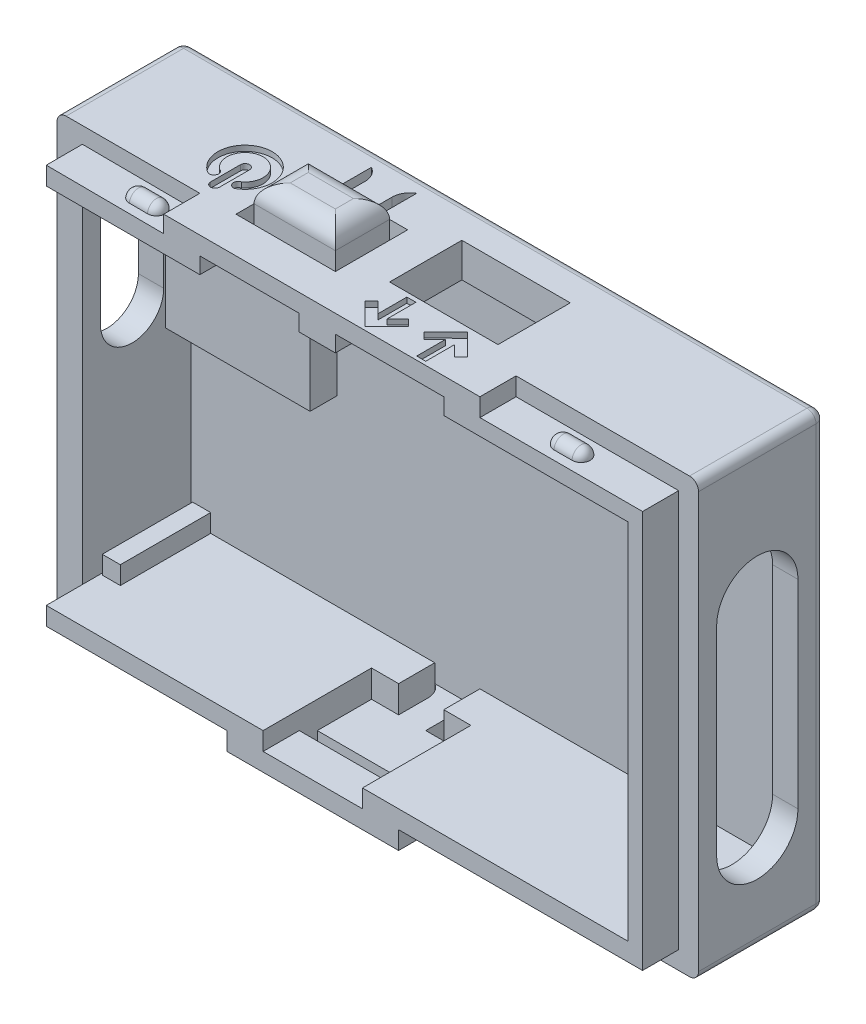
SolidWorks part; units mm, degrees
ref_plane "前视基准面" through (0, 0, 0) normal (0, 0, 1) x (1, 0, 0)
ref_plane "上视基准面" through (0, 0, 0) normal (0, 1, 0) x (1, 0, 0)
ref_plane "右视基准面" through (0, 0, 0) normal (1, 0, 0) x (0, 0, -1)
sketch "草图1" plane through (0, 0, 0) normal (0, 0, 1) x (1, 0, 0)
  line L5 (-17.75, 12) -> (17.75, 12)
  line L6 (-17.75, 12) -> (-17.75, -12)
  line L7 (-17.75, -12) -> (17.75, -12)
  line L8 (17.75, 12) -> (17.75, -12)
  line L9 (-17.75, 12) -> (17.75, -12) construction
  line L10 (-17.75, -12) -> (17.75, 12) construction
  point P0 (0, 0)
  dimension "D1" = 35.5
  dimension "D2" = 24
extrude "凸台-拉伸1" add sketch "草图1" along normal blind 7
sketch "草图2" plane through (0, 0, 7) normal (0, 0, 1) x (1, 0, 0)
  line L5 (-16.35, 11.1) -> (16.85, -11) construction
  line L6 (-16.35, -11) -> (16.85, 11.1) construction
  line L9 (-17.75, 12) -> (-17.75, -12) construction
  line L10 (-16.35, 11.1) -> (16.85, 11.1)
  line L11 (-16.35, 11.1) -> (-16.35, -11)
  line L12 (-16.35, -11) -> (16.85, -11)
  line L13 (16.85, 11.1) -> (16.85, -11)
  line L15 (17.75, 12) -> (-17.75, 12) construction
  line L16 (17.75, -12) -> (17.75, 12) construction
  point P0 (0, 0)
  dimension "D1" = 1.4
  dimension "D2" = 0.9
  dimension "D3" = 0.9
  dimension "D4" = 22.1
extrude "切除-拉伸1" cut sketch "草图2" against normal blind 6
sketch "草图3" plane through (-17.75, 0, 0) normal (-1, 0, 0) x (0, 0, 1)
  line L0 (4.25, 7.45) -> (4.25, 1.95) construction
  line L1 (6, 7.45) -> (6, 1.95)
  line L2 (2.5, 7.45) -> (2.5, 1.95)
  line L3 (0, 12) -> (0, -12) construction
  line L4 (7, 12) -> (0, 12) construction
  arc A0 (6, 7.45) -> (2.5, 7.45) centre (4.25, 7.45) ccw
  arc A1 (2.5, 1.95) -> (6, 1.95) centre (4.25, 1.95) ccw
  point P2 (4.25, 4.7)
  dimension "D3" = 5.5
  dimension "D4" = 4.55
  dimension "D1" = 2.5
  dimension "D2" = 3.5
extrude "切除-拉伸2" cut sketch "草图3" against normal blind 2
sketch "草图6" plane through (0, 0, 1) normal (0, 0, 1) x (1, 0, 0)
  line L14 (-16.35, 10.1) -> (15.85, 10.1)
  line L15 (-16.35, 11.1) -> (-16.35, -11) construction
  line L16 (15.85, 10.1) -> (15.85, -10)
  line L17 (15.85, -10) -> (-16.35, -10)
  line L18 (-16.35, -10) -> (-16.35, -11)
  line L19 (-16.35, -11) -> (16.85, -11)
  line L20 (16.85, -11) -> (16.85, 11.1)
  line L21 (16.85, 11.1) -> (-16.35, 11.1)
  line L22 (-16.35, 11.1) -> (-16.35, 10.1)
  dimension "D1" = 1
  dimension "D2" = 1
  dimension "D3" = 1
extrude "凸台-拉伸2" add sketch "草图6" along normal blind 6
sketch "草图7" plane through (0, 0, 1) normal (0, 0, 1) x (1, 0, 0)
  line L23 (15.85, 10.1) -> (10.85, 10.1)
  line L24 (15.85, 10.1) -> (15.85, 8.1)
  line L25 (15.85, 8.1) -> (10.85, 8.1)
  line L26 (10.85, 10.1) -> (10.85, 8.1)
  dimension "D3" = 5
  dimension "D8" = 2
extrude "凸台-拉伸3" add sketch "草图7" along normal blind 5
sketch "草图10" plane through (15.85, 0, 0) normal (-1, 0, 0) x (0, 0, 1)
  line L0 (3.75, -6.45) -> (3.75, 4.55) construction
  line L1 (1.5, -6.45) -> (1.5, 4.55)
  line L2 (6, -6.45) -> (6, 4.55)
  line L4 (7, -12) -> (0, -12) construction
  line L5 (7, -12) -> (7, 12) construction
  arc A0 (1.5, -6.45) -> (6, -6.45) centre (3.75, -6.45) ccw
  arc A1 (6, 4.55) -> (1.5, 4.55) centre (3.75, 4.55) ccw
  point P2 (3.75, -0.95)
  point P7 (3.75, 6.8)
  point P8 (3.75, -8.7)
  dimension "D2" = 15.5
  dimension "D1" = 4.5
  dimension "D3" = 1
  dimension "D4" = 3.3
extrude "切除-拉伸4" cut sketch "草图10" against normal blind 2
sketch "草图12" plane through (0, 0, 7) normal (0, 0, 1) x (1, 0, 0)
  line L0 (-16.35, 10.1) -> (-16.35, -10) construction
  line L8 (15.85, -10) -> (-16.35, -10) construction
  line L9 (-4.35, -10) -> (1.15, -10)
  line L10 (-4.35, -10) -> (-4.35, -12)
  line L11 (-4.35, -12) -> (1.15, -12)
  line L12 (1.15, -10) -> (1.15, -12)
  line L15 (-16.35, 10.1) -> (-16.35, -10) construction
  dimension "D1" = 12
  dimension "D2" = 17.5
  dimension "D3" = 2
extrude "切除-拉伸6" cut sketch "草图12" against normal blind 6
sketch "草图19" plane through (0, 0, 1) normal (0, 0, 1) x (1, 0, 0)
  line L0 (-16.35, 10.1) -> (10.85, 10.1) construction
  line L1 (-16.25, 10.1) -> (-8.25, 10.1)
  line L2 (-16.25, 10.1) -> (-16.25, 0.1)
  line L3 (-16.25, 0.1) -> (-8.25, 0.1)
  line L4 (-8.25, 10.1) -> (-8.25, 0.1)
  dimension "D1" = 8
  dimension "D2" = 0
  dimension "D3" = 10
extrude "USB支撑" add sketch "草图19" along normal blind 1.5
sketch "草图25" plane through (0, 0, 7) normal (0, 0, 1) x (1, 0, 0)
  line L0 (1.15, -12) -> (17.75, -12) construction
  line L2 (15.85, 8.1) -> (16.35, 8.1)
  line L3 (15.85, 8.1) -> (15.85, -10)
  line L4 (15.85, -10) -> (16.35, -10)
  line L5 (16.35, 8.1) -> (16.35, -10)
  line L7 (-16.35, 10.1) -> (15.85, 10.1) construction
  line L8 (15.85, 10.1) -> (15.85, -10) construction
  dimension "D1" = 2
  dimension "D2" = 2
  dimension "D3" = 0
  dimension "D4" = 0.5
extrude "切除-拉伸12" cut sketch "草图25" against normal blind 6
sketch "草图28" plane through (0, 0, 7) normal (0, 0, 1) x (1, 0, 0)
  line L0 (-16.35, 10.1) -> (15.85, 10.1) construction
  line L1 (-7.85, 10.1) -> (-2.35, 10.1)
  line L2 (-7.85, 10.1) -> (-7.85, 12)
  line L3 (-7.85, 12) -> (-2.35, 12)
  line L4 (-2.35, 10.1) -> (-2.35, 12)
  line L5 (17.75, 12) -> (-17.75, 12) construction
  line L6 (-16.35, 1.95) -> (-16.35, 7.45) construction
  dimension "D1" = 8.5
  dimension "D2" = 5.5
extrude "切除-拉伸13" cut sketch "草图28" against normal blind 6
sketch "草图29" plane through (0, 0, 7) normal (0, 0, 1) x (1, 0, 0)
  line L1 (-0.35, 10) -> (5.65, 10)
  line L2 (-0.35, 10) -> (-0.35, 12)
  line L3 (-0.35, 12) -> (5.65, 12)
  line L4 (5.65, 10) -> (5.65, 12)
  line L5 (17.75, 12) -> (-2.35, 12) construction
  line L8 (-16.35, 10.1) -> (-16.35, -10) construction
  dimension "D1" = 16
  dimension "D2" = 6
extrude "切除-拉伸14" cut sketch "草图29" against normal blind 5
sketch "草图34" plane through (0, 0, 1) normal (0, 0, 1) x (1, 0, 0)
  line L0 (16.35, -10) -> (1.15, -10) construction
  line L1 (-16.25, -9) -> (-15.25, -9)
  line L2 (-16.25, -9) -> (-16.25, -10)
  line L3 (-16.25, -10) -> (-15.25, -10)
  line L4 (-15.25, -9) -> (-15.25, -10)
  dimension "D1" = 1
  dimension "D2" = 1
extrude "凸台-拉伸10" add sketch "草图34" along normal blind 5
sketch "草图37" plane through (0, 0, 1) normal (0, 0, 1) x (1, 0, 0)
  line L0 (-4.35, -12) -> (1.15, -12) construction
  line L1 (-3.85, -12) -> (0.65, -12)
  line L2 (-3.85, -12) -> (-3.85, -10)
  line L3 (-3.85, -10) -> (0.65, -10)
  line L4 (0.65, -12) -> (0.65, -10)
  line L5 (1.15, -12) -> (1.15, -10) construction
  line L6 (-4.35, -10) -> (-4.35, -12) construction
  dimension "D1" = 0.5
  dimension "D2" = 0.5
  dimension "D3" = 2
extrude "凸台-拉伸12" add sketch "草图37" along normal blind 5.5
sketch "草图38" plane through (0, -12, 0) normal (0, -1, 0) x (1, 0, 0)
  line L1 (-3.85, 1) -> (-2.35, 1)
  line L2 (-3.85, 1) -> (-3.85, 3.5)
  line L3 (-3.85, 3.5) -> (-2.35, 3.5)
  line L4 (-2.35, 1) -> (-2.35, 3.5)
  line L5 (0.65, 1) -> (-0.85, 1)
  line L6 (0.65, 1) -> (0.65, 3.5)
  line L7 (0.65, 3.5) -> (-0.85, 3.5)
  line L8 (-0.85, 1) -> (-0.85, 3.5)
  dimension "D1" = 2.5
  dimension "D2" = 2.5
  dimension "D3" = 1.5
  dimension "D4" = 1.5
extrude "切除-拉伸16" cut sketch "草图38" against normal blind 2
sketch "草图39" plane through (0, 0, 6.5) normal (0, 0, 1) x (1, 0, 0)
  line L0 (0.65, -12) -> (0.65, -10) construction
  line L1 (-3.85, -10) -> (0.65, -10)
  line L2 (-3.85, -10) -> (-3.85, -11)
  line L3 (-3.85, -11) -> (0.65, -11)
  line L4 (0.65, -10) -> (0.65, -11)
  dimension "D1" = 1
extrude "切除-拉伸17" cut sketch "草图39" against normal blind 5.5
sketch "草图40" plane through (0, -12, 0) normal (0, -1, 0) x (1, 0, 0)
  line L0 (0.65, 6.5) -> (0.65, 3.5) construction
  line L1 (-3.85, 6.5) -> (0.65, 6.5)
  line L2 (-3.85, 6.5) -> (-3.85, 3.5)
  line L3 (-3.85, 3.5) -> (0.65, 3.5)
  line L4 (0.65, 6.5) -> (0.65, 3.5)
  line L6 (-3.85, 6.5) -> (0.65, 6.5) construction
  dimension "D1" = 3
  dimension "D2" = 0
  dimension "D3" = 4.5
extrude "凸台-拉伸13" add sketch "草图40" along normal blind 1.5
fillet "圆角2" radius 1 4 edges at (-1.6, -13.5, 3.5) (0.65, -13.5, 5) (-1.6, -13.5, 6.5) (-3.85, -13.5, 5)
sketch "草图41" plane through (0, 0, 1) normal (0, 0, 1) x (1, 0, 0)
  line L0 (-2.35, 12) -> (-7.85, 12) construction
  line L1 (-7.35, 12) -> (-2.85, 12)
  line L2 (-7.35, 12) -> (-7.35, 10)
  line L3 (-7.35, 10) -> (-2.85, 10)
  line L4 (-2.85, 12) -> (-2.85, 10)
  line L5 (-2.35, 10.1) -> (-2.35, 12) construction
  line L6 (-7.85, 12) -> (-7.85, 10.1) construction
  dimension "D1" = 0.5
  dimension "D2" = 0.5
  dimension "D3" = 2
extrude "凸台-拉伸14" add sketch "草图41" along normal blind 5.5
sketch "草图42" plane through (0, 12, 0) normal (0, 1, 0) x (1, 0, 0)
  line L1 (-7.35, -1) -> (-5.85, -1)
  line L2 (-7.35, -1) -> (-7.35, -3.5)
  line L3 (-7.35, -3.5) -> (-5.85, -3.5)
  line L4 (-5.85, -1) -> (-5.85, -3.5)
  line L5 (-2.85, -1) -> (-4.35, -1)
  line L6 (-2.85, -1) -> (-2.85, -3.5)
  line L7 (-2.85, -3.5) -> (-4.35, -3.5)
  line L8 (-4.35, -1) -> (-4.35, -3.5)
  dimension "D1" = 1.5
  dimension "D2" = 1.5
  dimension "D3" = 2.5
  dimension "D4" = 2.5
extrude "切除-拉伸18" cut sketch "草图42" against normal blind 2
sketch "草图43" plane through (0, 0, 6.5) normal (0, 0, 1) x (1, 0, 0)
  line L0 (-2.85, 10) -> (-2.85, 12) construction
  line L1 (-7.35, 10) -> (-2.85, 10)
  line L2 (-7.35, 10) -> (-7.35, 11)
  line L3 (-7.35, 11) -> (-2.85, 11)
  line L4 (-2.85, 10) -> (-2.85, 11)
extrude "切除-拉伸19" cut sketch "草图43" against normal blind 5.5
sketch "草图44" plane through (0, 12, 0) normal (0, 1, 0) x (1, 0, 0)
  line L0 (-2.85, -6.5) -> (-2.85, -3.5) construction
  line L1 (-7.35, -6.5) -> (-2.85, -6.5)
  line L2 (-7.35, -6.5) -> (-7.35, -3.5)
  line L3 (-7.35, -3.5) -> (-2.85, -3.5)
  line L4 (-2.85, -6.5) -> (-2.85, -3.5)
  dimension "D1" = 3
extrude "凸台-拉伸15" add sketch "草图44" along normal blind 1.5
fillet "圆角3" radius 1 4 edges at (-2.85, 13.5, 5) (-5.1, 13.5, 3.5) (-7.35, 13.5, 5) (-5.1, 13.5, 6.5)
sketch "草图45" plane through (0, 0, 7) normal (0, 0, 1) x (1, 0, 0)
  line L0 (-7.85, 10.1) -> (-16.35, 10.1)
  line L1 (-16.35, 10.1) -> (-16.35, 11.1)
  line L2 (-16.35, 11.1) -> (-7.85, 11.05)
  line L3 (-7.85, 12) -> (-7.85, 10.1) construction
  line L5 (-0.35, 12) -> (-0.35, 10.1) construction
  line L10 (-2.35, 10.1) -> (-0.35, 10.1)
  line L12 (-2.25, 11.05) -> (-0.35, 11.05)
  line L13 (-0.35, 10.1) -> (-0.35, 11.05)
  line L14 (1.25, -11) -> (-16.35, -11)
  line L16 (5.65, 10.1) -> (5.65, 11)
  line L17 (5.65, 11) -> (16.65, 11)
  line L18 (16.65, 10) -> (16.65, 11)
  line L23 (-16.35, -11) -> (-16.35, -10)
  line L24 (-16.35, -10) -> (1.15, -10)
  line L25 (-7.85, 10.1) -> (-2.35, 10.1)
  line L26 (-2.25, 11.05) -> (-7.85, 11.05)
  line L27 (16.65, 10) -> (16.65, -11)
  line L28 (16.65, -11) -> (1.25, -11)
  line L29 (1.15, -10) -> (15.85, -10)
  line L31 (16.35, -10) -> (1.15, -10) construction
  line L32 (15.85, -10) -> (15.85, 10.1)
  line L33 (15.85, 10.1) -> (5.65, 10.1)
  dimension "D1" = 1
  dimension "D4" = 1
  dimension "D5" = 11
extrude "凸台-拉伸16" add sketch "草图45" along normal blind 2
sketch "草图46" plane through (0, -11, 0) normal (0, -1, 0) x (1, 0, 0)
  line L1 (-11.25, 8.5) -> (-10.25, 8.5)
  line L2 (-11.75, 8) -> (-9.75, 8)
  line L4 (-16.35, 7) -> (-4.35, 7) construction
  line L5 (-17.75, 7) -> (-17.75, 0) construction
  arc A4 (-11.75, 8) -> (-11.25, 8.5) centre (-11.25, 8) cw
  arc A5 (-10.25, 8.5) -> (-9.75, 8) centre (-10.25, 8) cw
  point P4 (-10.75, 8.5)
  point P7 (-10.75, 8)
  dimension "D1" = 2
  dimension "D2" = 0.5
  dimension "D4" = 1
  dimension "D3" = 1
  dimension "D5" = 6
revolve "旋转1" add sketch "草图46" angle 360 about L2
sketch "草图47" plane through (0, -11, 0) normal (0, -1, 0) x (1, 0, 0)
  line L0 (11.75, 8) -> (9.75, 8)
  line L1 (1.15, 7) -> (17.75, 7) construction
  line L2 (10.25, 8.5) -> (11.25, 8.5)
  line L4 (17.75, 7) -> (17.75, 0) construction
  arc A1 (10.25, 8.5) -> (9.75, 8) centre (10.25, 8) ccw
  arc A2 (11.25, 8.5) -> (11.75, 8) centre (11.25, 8) cw
  point P8 (10.75, 8.5)
  point P9 (10.75, 8)
  dimension "D2" = 1
  dimension "D1" = 2
  dimension "D3" = 1
  dimension "D4" = 6
  dimension "D5" = 0.5
revolve "旋转2" add sketch "草图47" angle 360 about L0
sketch "草图48" plane through (0, 11.05, 0) normal (0, 1, 0) x (1, 0, 0)
  line L0 (-12.75, -8) -> (-10.75, -8)
  line L1 (-12.25, -8.5) -> (-11.25, -8.5)
  line L2 (-0.35, -9) -> (-7.85, -9) construction
  line L5 (-17.75, -7) -> (-17.75, 0) construction
  arc A1 (-12.25, -8.5) -> (-12.75, -8) centre (-12.25, -8) cw
  arc A2 (-11.25, -8.5) -> (-10.75, -8) centre (-11.25, -8) ccw
  point P8 (-11.75, -8)
  point P9 (-11.75, -8.5)
  dimension "D2" = 1
  dimension "D1" = 2
  dimension "D3" = 5
  dimension "D4" = 1
  dimension "D5" = 0.5
revolve "旋转3" add sketch "草图48" angle 360 about L0
sketch "草图49" plane through (0, 11, 0) normal (0, 1, 0) x (1, 0, 0)
  line L0 (10.75, -8) -> (12.75, -8)
  line L1 (16.65, -9) -> (5.65, -9) construction
  line L2 (11.25, -8.5) -> (12.25, -8.5)
  line L5 (17.75, -7) -> (17.75, 0) construction
  arc A1 (11.25, -8.5) -> (10.75, -8) centre (11.25, -8) cw
  arc A2 (12.25, -8.5) -> (12.75, -8) centre (12.25, -8) ccw
  point P6 (0, 0)
  point P8 (11.75, -8.5)
  point P9 (11.75, -8)
  dimension "D2" = 1
  dimension "D1" = 2
  dimension "D3" = 1
  dimension "D4" = 0.5
  dimension "D5" = 5
revolve "旋转4" add sketch "草图49" angle 360 about L0
sketch "草图50" plane through (0, 10.1, 0) normal (0, -1, 0) x (1, 0, 0)
  line L0 (-16.35, 9) -> (-0.35, 9) construction
  line L1 (-7.85, 7) -> (-2.35, 7)
  line L2 (-7.85, 7) -> (-7.85, 9)
  line L3 (-7.85, 9) -> (-2.35, 9)
  line L4 (-2.35, 7) -> (-2.35, 9)
extrude "切除-拉伸20" cut sketch "草图50" against normal blind 2
sketch "草图51" plane through (0, -11, 0) normal (0, -1, 0) x (1, 0, 0)
  line L0 (-16.35, 9) -> (16.65, 9) construction
  line L1 (-4.35, 7) -> (1.15, 7)
  line L2 (-4.35, 7) -> (-4.35, 9)
  line L3 (-4.35, 9) -> (1.15, 9)
  line L4 (1.15, 7) -> (1.15, 9)
extrude "切除-拉伸21" cut sketch "草图51" against normal blind 2
sketch "草图54" plane through (0, 0, 7) normal (0, 0, 1) x (1, 0, 0)
  line L1 (-7.85, 11.05) -> (-9.85, 11.05)
  line L2 (-7.85, 11.05) -> (-7.85, 12)
  line L3 (-7.85, 12) -> (-9.85, 12)
  line L4 (-9.85, 11.05) -> (-9.85, 12)
  dimension "D1" = 2
extrude "凸台-拉伸19" add sketch "草图54" along normal blind 2
sketch "草图55" plane through (-7.85, 0, 0) normal (1, 0, 0) x (0, 0, -1)
  line L5 (-9, 12) -> (-7, 12)
  line L6 (-9, 12) -> (-9, 11)
  line L7 (-9, 11) -> (-7, 11)
  line L8 (-7, 12) -> (-7, 11)
  dimension "D1" = 1
  dimension "D2" = 2
extrude "凸台-拉伸20" add sketch "草图55" along normal blind 15.5
sketch "草图56" plane through (0, 0, 7) normal (0, 0, 1) x (1, 0, 0)
  line L0 (-16.35, -11) -> (-4.35, -11) construction
  line L1 (-4.35, -12) -> (-6.35, -12)
  line L2 (-4.35, -12) -> (-4.35, -11)
  line L3 (-4.35, -11) -> (-6.35, -11)
  line L4 (-6.35, -12) -> (-6.35, -11)
  dimension "D1" = 2
extrude "凸台-拉伸21" add sketch "草图56" along normal blind 2
sketch "草图57" plane through (-4.35, 0, 0) normal (1, 0, 0) x (0, 0, -1)
  line L1 (-9, -12) -> (-7, -12)
  line L2 (-9, -12) -> (-9, -11)
  line L3 (-9, -11) -> (-7, -11)
  line L4 (-7, -12) -> (-7, -11)
  dimension "D1" = 1
  dimension "D2" = 2
extrude "凸台-拉伸22" add sketch "草图57" along normal blind 7.5
sketch "草图58" plane through (0, 0, 1) normal (0, 0, 1) x (1, 0, 0)
  line L0 (-0.85, -12) -> (1.15, -12) construction
  line L1 (-7.85, 12) -> (-6.35, 12)
  line L2 (-7.85, 12) -> (-7.85, 10.1)
  line L3 (-7.85, 10.1) -> (-6.35, 10.1)
  line L4 (-6.35, 12) -> (-6.35, 10.1)
  line L5 (-2.35, 12) -> (-3.85, 12)
  line L6 (-2.35, 12) -> (-2.35, 10.1)
  line L7 (-2.35, 10.1) -> (-3.85, 10.1)
  line L8 (-3.85, 12) -> (-3.85, 10.1)
  line L9 (-4.35, -12) -> (-2.85, -12)
  line L10 (-4.35, -12) -> (-4.35, -10)
  line L11 (-4.35, -10) -> (-2.85, -10)
  line L12 (-2.85, -12) -> (-2.85, -10)
  line L13 (1.15, -10) -> (-0.35, -10)
  line L14 (1.15, -10) -> (1.15, -12)
  line L15 (1.15, -12) -> (-0.35, -12)
  line L16 (-0.35, -10) -> (-0.35, -12)
  dimension "D1" = 1.5
  dimension "D2" = 1.5
  dimension "D3" = 1.9
  dimension "D4" = 1.9
  dimension "D5" = 2
  dimension "D6" = 1.5
  dimension "D7" = 1.5
extrude "凸台-拉伸24" add sketch "草图58" along normal blind 2
sketch "草图59" plane through (0, 0, 7) normal (0, 0, -1) x (-1, 0, 0)
  line L1 (-5.65, 12) -> (0.35, 12)
  line L2 (-5.65, 12) -> (-5.65, 11)
  line L3 (-5.65, 11) -> (0.35, 11)
  line L4 (0.35, 12) -> (0.35, 11)
extrude "凸台-拉伸25" add sketch "草图59" along normal blind 1
sketch "草图60" plane through (0, 12, 0) normal (0, 1, 0) x (1, 0, 0)
  line L0 (4.45, -8.8) -> (4.45, -7.2)
  line L1 (4.45, -7.2) -> (5.0493, -7.8)
  line L2 (5.0493, -7.8) -> (5.4031, -7.4466)
  line L3 (5.4031, -7.4466) -> (4.2007, -6.2429)
  line L4 (4.2007, -6.2429) -> (2.996, -7.4463)
  line L5 (2.996, -7.4463) -> (3.3493, -7.8)
  line L6 (3.3493, -7.8) -> (3.95, -7.2)
  line L7 (3.95, -7.2) -> (3.95, -8.8)
  line L8 (3.95, -8.8) -> (4.45, -8.8)
  line L9 (1.35, -6.2429) -> (0.85, -6.2429)
  line L10 (0.85, -6.2429) -> (0.85, -7.8429)
  line L11 (0.85, -7.8429) -> (0.2507, -7.2429)
  line L12 (0.2507, -7.2429) -> (-0.1031, -7.5963)
  line L13 (-0.1031, -7.5963) -> (1.0993, -8.8)
  line L14 (1.0993, -8.8) -> (2.304, -7.5966)
  line L15 (2.304, -7.5966) -> (1.9507, -7.2429)
  line L16 (1.9507, -7.2429) -> (1.35, -7.8429)
  line L17 (1.35, -7.8429) -> (1.35, -6.2429)
  line L18 (7.65, -9) -> (-9.85, -9) construction
  line L19 (5.65, -2) -> (5.65, -6) construction
  line L20 (-0.35, -2) -> (-0.35, -6) construction
  point P9 (4.2, -8.8)
  dimension "D1" = 0.5
  dimension "D2" = 0.5
  dimension "D3" = 0.5
  dimension "D4" = 1.6
  dimension "D5" = 1.6
  dimension "D6" = 1
  dimension "D7" = 1
  dimension "D8" = 0.5
  dimension "D9" = 0.5
  dimension "D10" = 0.5
  dimension "D11" = 1
  dimension "D12" = 1
  dimension "D13" = 1.6
  dimension "D14" = 1.6
  dimension "D15" = 0.2
  dimension "D16" = 0.2
  dimension "D17" = 1.2
  dimension "D18" = 1.2
sketch "草图61" plane through (0, 12, 0) normal (0, 1, 0) x (1, 0, 0)
  line L1 (-7.85, -3) -> (-7.85, -7) construction
  line L2 (17.75, 0) -> (-17.75, 0) construction
  line L3 (-9.6, -6.1596) -> (-9.6, -4.5)
  line L4 (-10.1, -6.1596) -> (-10.1, -4.5)
  arc A0 (-9.1017, -5.8) -> (-10.5983, -5.8) centre (-9.85, -4.5) ccw
  arc A1 (-9.25, -5.3) -> (-10.45, -5.3) centre (-9.85, -4.5) ccw
  arc A4 (-9.6, -6.1596) -> (-10.1, -6.1596) centre (-9.85, -6.1596) cw
  arc A5 (-9.6, -4.5) -> (-10.1, -4.5) centre (-9.85, -4.5) ccw
  arc A8 (-9.1017, -5.8) -> (-9.25, -5.3) centre (-9.1758, -5.55) cw
  arc A9 (-10.5983, -5.8) -> (-10.45, -5.3) centre (-10.5242, -5.55) ccw
  dimension "D1" = 1.5
  dimension "D2" = 1
  dimension "D7" = 5.3
  dimension "D3" = 4.5
  dimension "D4" = 4.5
  dimension "D5" = 2
  dimension "D6" = 2
  dimension "D8" = 5.3
  dimension "D9" = 5.8
  dimension "D10" = 5.8
  dimension "D11" = 0.5
extrude "切除-拉伸22" cut sketch "草图61" against normal blind 0.3
extrude "切除-拉伸23" cut sketch "草图60" against normal blind 0.3
fillet "圆角4" radius 0.5 8 edges at (0, -12, 0) (17.75, 0, 0) (0, 12, 0) (-17.75, 0, 0) (-17.75, 12, 3.5) (-17.75, -12, 3.5) (17.75, -12, 3.5) (17.75, 12, 3.5)
fillet "圆角5" radius 1 4 edges at (-2.35, -11.5, 1) (-0.85, -11.5, 1) (-5.85, 11.5, 1) (-4.35, 11.5, 1)
equation "\"1、\"=0.989542"
